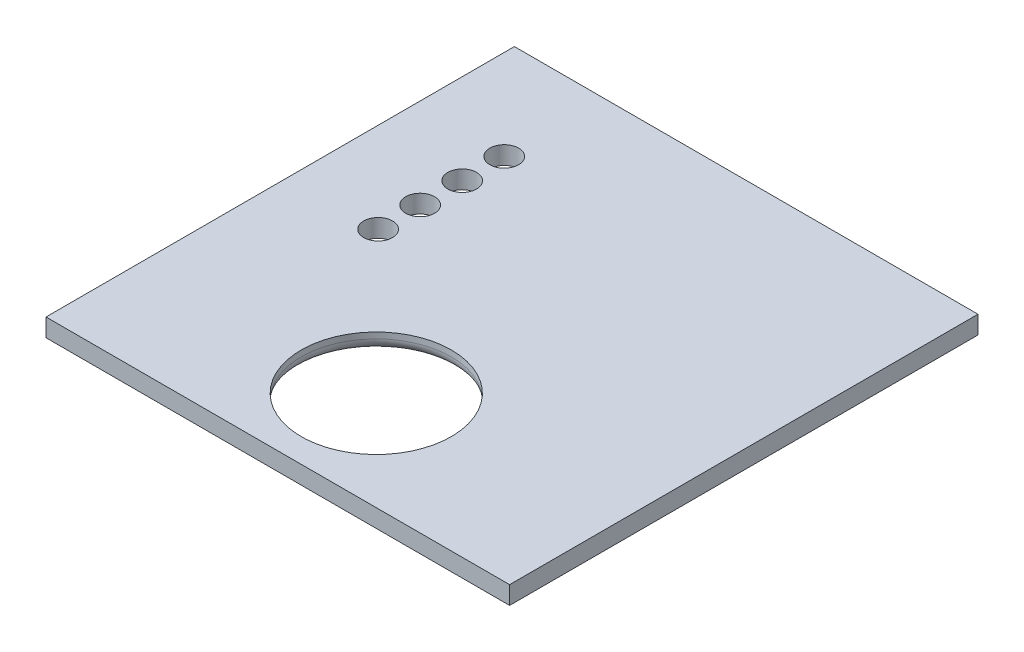
SolidWorks part; units mm, degrees
ref_plane "Front" through (0, 0, 0) normal (0, 0, 1) x (1, 0, 0)
ref_plane "Top" through (0, 0, 0) normal (0, 1, 0) x (1, 0, 0)
ref_plane "Right" through (0, 0, 0) normal (1, 0, 0) x (0, 0, -1)
sketch "Эскиз1" plane through (0, 0, 0) normal (0, 1, 0) x (1, 0, 0)
  line L1 (-158.1764, 86.5492) -> (-80.9764, 86.5492)
  line L2 (-158.1764, 86.5492) -> (-158.1764, 8.5492)
  line L3 (-158.1764, 8.5492) -> (-80.9764, 8.5492)
  line L4 (-80.9764, 86.5492) -> (-80.9764, 8.5492)
  dimension "D1" = 77.2
  dimension "D2" = 78
extrude "Бобышка-Вытянуть1" add sketch "Эскиз1" along normal blind 3
sketch "Эскиз2" plane through (0, 3, 0) normal (0, 1, 0) x (1, 0, 0)
  line L0 (-158.1764, 86.5492) -> (-158.1764, 8.5492) construction
  line L1 (-158.1764, 8.5492) -> (-80.9764, 8.5492) construction
  circle A0 centre (-119.5764, 22.5492) radius 9.75
  dimension "D1" = 38.6
  dimension "D2" = 14
extrude "Вырез-Вытянуть1" cut sketch "Эскиз2" along normal blind 87 and the other way blind 71
sketch "Эскиз3" plane through (0, 3, 0) normal (0, 1, 0) x (1, 0, 0)
  line L0 (-158.1764, 86.5492) -> (-158.1764, 8.5492) construction
  circle A0 centre (-143.1764, 48.8556) radius 2.4
  circle A1 centre (-143.1764, 55.8556) radius 2.4
  circle A2 centre (-138.1048, 0) radius 2.4
  circle A3 centre (-138.1048, 0) radius 2.4
  circle A4 centre (-143.1764, 69.8556) radius 2.4
  circle A5 centre (-143.1764, 62.8556) radius 2.4
  dimension "D1" = 15
  dimension "D2" = 15
  dimension "D3" = 7
  dimension "D4" = 15
  dimension "D5" = 7
  dimension "D6" = 15
  dimension "D7" = 7
extrude "Вырез-Вытянуть3" cut sketch "Эскиз3" against normal blind 207 and the other way blind 150 contours A4 | A5 | A1 | A0 region at (-143.1764, 3, -48.8556) region at (-143.1764, 3, -55.8556) region at (-143.1764, 3, -69.8556) region at (-143.1764, 3, -62.8556)
sketch "Эскиз4" plane through (0, 0, 0) normal (0, 1, 0) x (1, 0, 0)
  line L1 (-36.8822, 61.3775) -> (43.1178, 61.3775)
  line L2 (-36.8822, 61.3775) -> (-36.8822, 9.3775)
  line L3 (-36.8822, 9.3775) -> (43.1178, 9.3775)
  line L4 (43.1178, 61.3775) -> (43.1178, 9.3775)
  dimension "D1" = 80
  dimension "D2" = 52
sketch "Эскиз11" plane through (0, 0, 0) normal (0, -1, 0) x (1, 0, 0)
  line L1 (-102.0742, -34.8588) -> (-136.4354, -34.8588)
  line L2 (-102.0742, -34.8588) -> (-102.0742, -11.7107)
  line L3 (-102.0742, -11.7107) -> (-136.4354, -11.7107)
  line L4 (-136.4354, -34.8588) -> (-136.4354, -11.7107)
extrude "Бобышка-Вытянуть4" add sketch "Эскиз11" against normal blind 3
ref_plane "Плоскость2" through (-80.9764, 3, -8.5492) normal (0, 0, -1) x (-1, 0, 0)
sketch "Эскиз13" plane through (0, 3, 0) normal (0, 1, 0) x (1, 0, 0)
  line L0 (-158.1764, 8.5492) -> (-80.9764, 8.5492) construction
  line L1 (-158.1764, 86.5492) -> (-158.1764, 8.5492) construction
  circle A0 centre (-119.6764, 27.5492) radius 12
  dimension "D1" = 19
  dimension "D2" = 38.5
extrude "Вырез-Вытянуть10" cut sketch "Эскиз13" against normal blind 10 and the other way blind 17
chamfer "Фаска4" distance 6 angle 45 1 edges at (-119.6764, 0, -15.5492)
sketch "Эскиз14" plane through (0, 3, 0) normal (0, 1, 0) x (1, 0, 0)
  line L1 (-138.687, 45.7397) -> (-100.499, 45.7397)
  line L2 (-138.687, 45.7397) -> (-138.687, 11.5184)
  line L3 (-138.687, 11.5184) -> (-100.499, 11.5184)
  line L4 (-100.499, 45.7397) -> (-100.499, 11.5184)
extrude "Бобышка-Вытянуть5" add sketch "Эскиз14" against normal blind 3
sketch "Эскиз15" plane through (0, 3, 0) normal (0, 1, 0) x (1, 0, 0)
  line L0 (-158.1764, 86.5492) -> (-158.1764, 8.5492) construction
  line L1 (-158.1764, 8.5492) -> (-80.9764, 8.5492) construction
  circle A0 centre (-119.6764, 25.0492) radius 12.5
  point P2 (-213.9933, 81.9719)
  dimension "D1" = 38.5
  dimension "D2" = 16.5
extrude "Вырез-Вытянуть11" cut sketch "Эскиз15" against normal blind 12256 and the other way blind 644
sketch "Эскиз16" plane through (0, 0, 0) normal (0, -1, 0) x (1, 0, 0)
  line L1 (-128.4878, -12.2208) -> (-110.4405, -12.2208)
  line L2 (-128.4878, -12.2208) -> (-128.4878, -9.2102)
  line L3 (-128.4878, -9.2102) -> (-110.4405, -9.2102)
  line L4 (-110.4405, -12.2208) -> (-110.4405, -9.2102)
extrude "Бобышка-Вытянуть6" add sketch "Эскиз16" against normal blind 3 and the other way blind 1
sketch "Эскиз17" plane through (0, 0, 0) normal (0, -1, 0) x (-1, 0, 0)
  line L1 (109.9599, 8.9153) -> (129.6309, 8.9153)
  line L2 (109.9599, 8.9153) -> (109.9599, 12.5764)
  line L3 (109.9599, 12.5764) -> (129.6309, 12.5764)
  line L4 (129.6309, 8.9153) -> (129.6309, 12.5764)
extrude "Вырез-Вытянуть12" cut sketch "Эскиз17" along normal blind 1
fillet "Скругление1" radius 2 1 edges at (-119.6764, 0, -12.5492)
